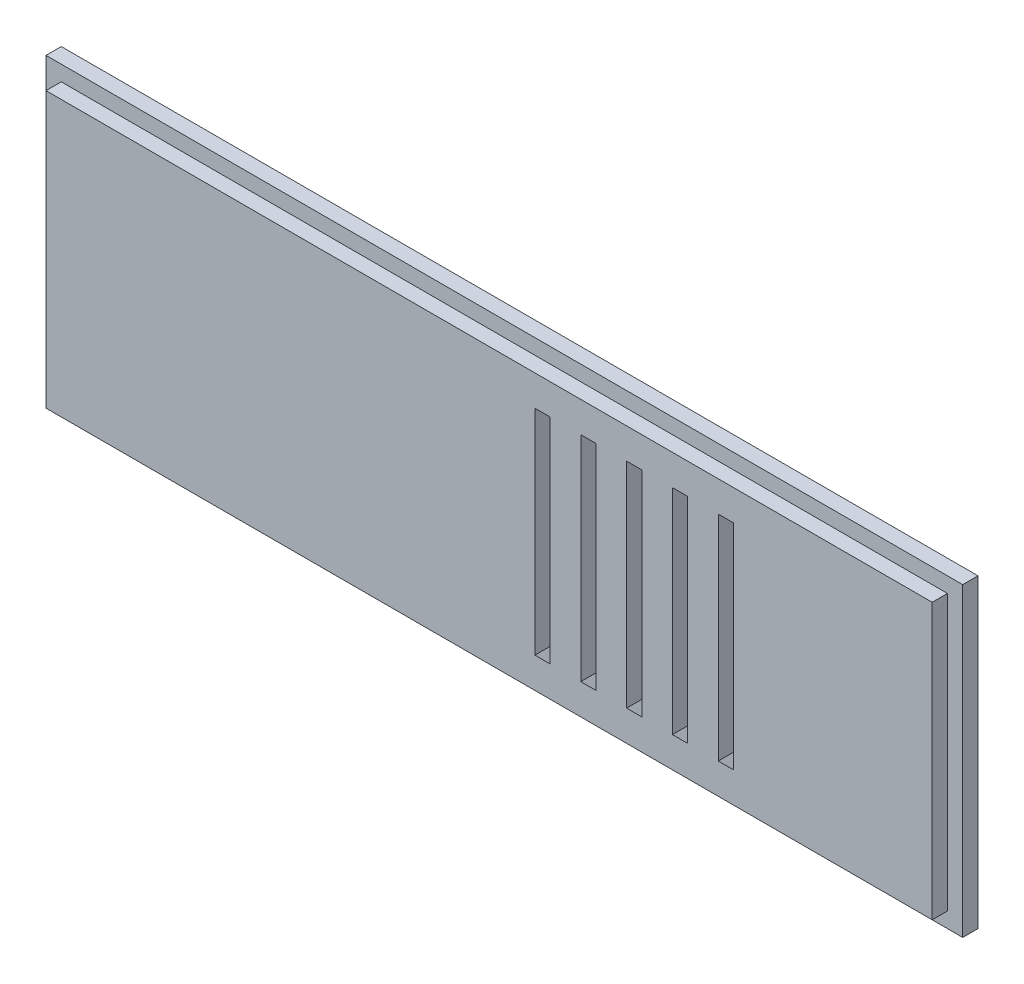
SolidWorks part; units mm, degrees
ref_plane "Front Plane" through (0, 0, 0) normal (0, 0, 1) x (1, 0, 0)
ref_plane "Top Plane" through (0, 0, 0) normal (0, 1, 0) x (1, 0, 0)
ref_plane "Right Plane" through (0, 0, 0) normal (1, 0, 0) x (0, 0, -1)
sketch "Sketch1" plane through (0, 0, 0) normal (0, 0, 1) x (1, 0, 0)
  line L0 (-30, 0) -> (30, 0) construction
  line L1 (-30, -10) -> (30, -10)
  line L2 (-30, -10) -> (-30, 10)
  line L3 (-30, 10) -> (30, 10)
  line L4 (30, -10) -> (30, 10)
  line L5 (0, 10) -> (0, -10) construction
  point P6 (0, 0)
  dimension "D1" = 20
  dimension "D2" = 60
extrude "Boss-Extrude1" add sketch "Sketch1" along normal blind 1
sketch "Sketch2" plane through (0, 0, 1) normal (0, 0, 1) x (1, 0, 0)
  line L0 (-29, 9) -> (-29, -9)
  line L1 (-29, -9) -> (29, -9)
  line L2 (29, -9) -> (29, 9)
  line L3 (29, 9) -> (-29, 9)
extrude "Boss-Extrude2" add sketch "Sketch2" along normal blind 1
sketch "Sketch3" plane through (0, 0, 0) normal (0, 0, -1) x (-1, 0, 0)
  line L0 (-30, 0) -> (-16, 0) construction
  line L1 (-30, -10) -> (-30, 10) construction
  line L2 (-16, -7) -> (-16, 7)
  line L3 (-16, 7) -> (-15, 7)
  line L4 (-15, 7) -> (-15, -7)
  line L5 (-15, -7) -> (-16, -7)
  line L6 (-12, -7) -> (-13, -7)
  line L7 (-12, 7) -> (-12, -7)
  line L8 (-13, 7) -> (-12, 7)
  line L9 (-13, -7) -> (-13, 7)
  line L10 (-9, -7) -> (-10, -7)
  line L11 (-9, 7) -> (-9, -7)
  line L12 (-10, 7) -> (-9, 7)
  line L13 (-10, -7) -> (-10, 7)
  line L14 (-6, -7) -> (-7, -7)
  line L15 (-6, 7) -> (-6, -7)
  line L16 (-7, 7) -> (-6, 7)
  line L17 (-7, -7) -> (-7, 7)
  line L18 (-3, -7) -> (-4, -7)
  line L19 (-3, 7) -> (-3, -7)
  line L20 (-4, 7) -> (-3, 7)
  line L21 (-4, -7) -> (-4, 7)
  point P8 (-16, 0)
  dimension "D1" = 5
extrude "Cut-Extrude1" cut sketch "Sketch3" against normal blind 4
chamfer "Chamfer1" distance 1 distance2 2 20 edges at (3.5, 7, 0) (4, 0, 0) (3, 0, 0) (3.5, -7, 0) (7, 0, 0) (6.5, 7, 0) (6, 0, 0) (6.5, -7, 0) (9.5, -7, 0) (9, 0, 0) (9.5, 7, 0) (10, 0, 0) (12.5, 7, 0) (12, 0, 0) (12.5, -7, 0) (13, 0, 0) (15.5, -7, 0) (15, 0, 0) (15.5, 7, 0) (16, 0, 0) first distance on face at (15.5, 0, 0)
